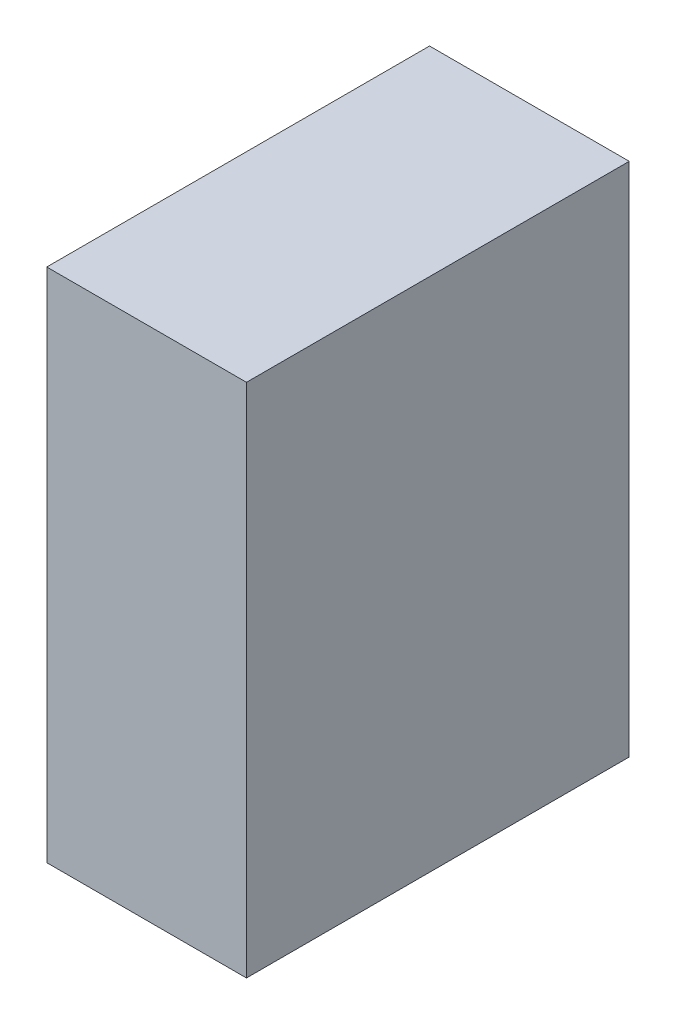
SolidWorks part; units mm, degrees
ref_plane "Front Plane" through (0, 0, 0) normal (0, 0, 1) x (1, 0, 0)
ref_plane "Top Plane" through (0, 0, 0) normal (0, 1, 0) x (1, 0, 0)
ref_plane "Right Plane" through (0, 0, 0) normal (1, 0, 0) x (0, 0, -1)
sketch "Sketch1" plane through (0, 0, 0) normal (1, 0, 0) x (0, 0, -1)
  line L1 (-41.0235, 72.9307) -> (105.0265, 72.9307)
  line L2 (-41.0235, 72.9307) -> (-41.0235, -123.9193)
  line L3 (-41.0235, -123.9193) -> (105.0265, -123.9193)
  line L4 (105.0265, 72.9307) -> (105.0265, -123.9193)
  dimension "D1" = 146.05
  dimension "D2" = 196.85
extrude "Boss-Extrude1" add sketch "Sketch1" along normal blind 76.2
sketch "Sketch2" plane through (0, -123.9193, 0) normal (0, -1, 0) x (1, 0, 0)
  circle A0 centre (19.96, 29.5535) radius 3.175 construction
  circle A1 centre (28.8421, 29.1795) radius 3.175 construction
  circle A2 centre (19.96, 29.5535) radius 3.175
  circle A3 centre (28.8421, 29.1795) radius 3.175
extrude "Cut-Extrude1" cut sketch "Sketch2" against normal blind 74.568
sketch "Sketch3" plane through (0, -123.9193, 0) normal (0, -1, 0) x (1, 0, 0)
  circle A0 centre (28.8406, 29.1454) radius 3.9688 construction
  circle A1 centre (19.96, 29.5535) radius 3.9688 construction
  circle A2 centre (28.8406, 29.1454) radius 3.9688
  circle A3 centre (19.96, 29.5535) radius 3.9688
extrude "Cut-Extrude2" cut sketch "Sketch3" against normal blind 50.568
sketch "Sketch4" plane through (0, -123.9193, 0) normal (0, -1, 0) x (1, 0, 0)
  circle A0 centre (34.46, -30.4465) radius 3.175 construction
  circle A1 centre (34.46, -30.4465) radius 3.175
extrude "Cut-Extrude3" cut sketch "Sketch4" against normal blind 39.268
sketch "Sketch5" plane through (0, -123.9193, 0) normal (0, -1, 0) x (1, 0, 0)
  circle A0 centre (34.46, -30.4465) radius 3.9688 construction
  circle A1 centre (34.46, -30.4465) radius 3.9688
extrude "Cut-Extrude4" cut sketch "Sketch5" against normal blind 6.268
sketch "Sketch6" plane through (0, 0, -105.0265) normal (0, 0, -1) x (-1, 0, 0)
  circle A0 centre (-24.96, -56.1513) radius 4 construction
  circle A1 centre (-24.96, 13.8487) radius 4 construction
  circle A2 centre (-24.96, -56.1513) radius 4
  circle A3 centre (-24.96, 13.8487) radius 4
extrude "Cut-Extrude5" cut sketch "Sketch6" against normal blind 13.08
sketch "Sketch7" plane through (0, 72.9307, 0) normal (0, 1, 0) x (1, 0, 0)
  point P0 (76.2, 105.0265)
